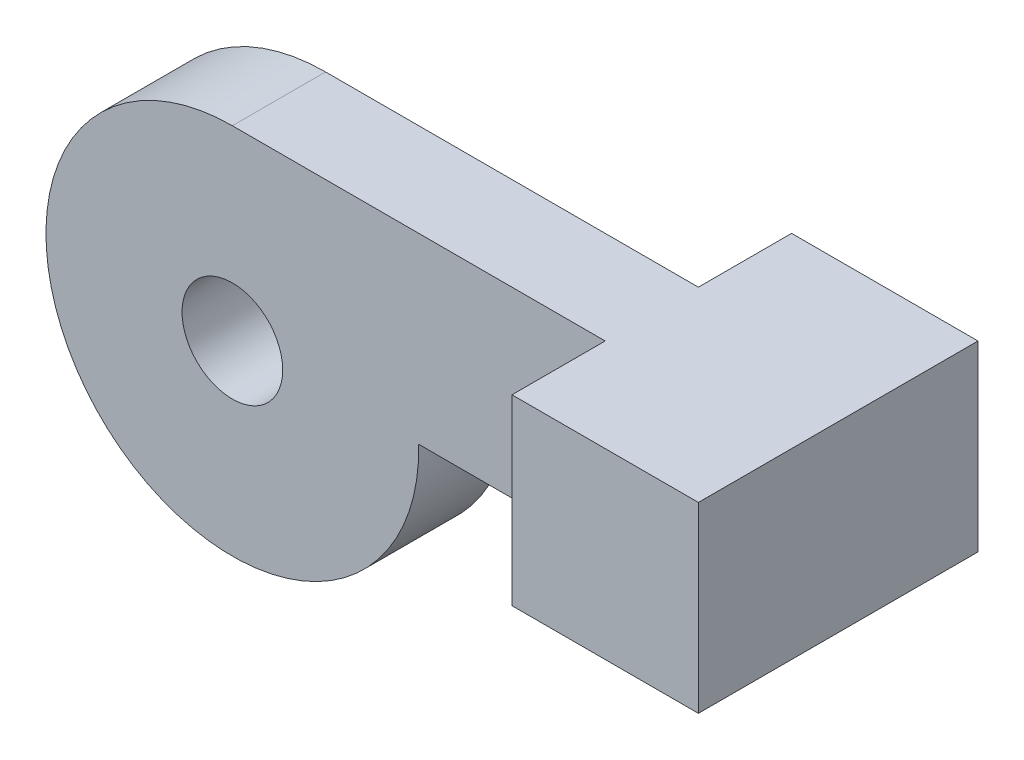
SolidWorks part; units mm, degrees
ref_plane "Front Plane" through (0, 0, 0) normal (0, 0, 1) x (1, 0, 0)
ref_plane "Top Plane" through (0, 0, 0) normal (0, 1, 0) x (1, 0, 0)
ref_plane "Right Plane" through (0, 0, 0) normal (1, 0, 0) x (0, 0, -1)
sketch "Sketch1" plane through (0, 0, 0) normal (0, 0, 1) x (1, 0, 0)
  line L5 (0, 12.7) -> (38.1, 12.7)
  line L6 (38.1, 12.7) -> (38.1, 0.254)
  line L7 (38.1, 0.254) -> (12.6975, 0.254)
  circle A2 centre (0, 0) radius 3.429
  arc A3 (0, 12.7) -> (12.6975, 0.254) centre (0, 0) ccw
  dimension "D3" = 6.858
  dimension "D5" = 25.4
  dimension "D2" = 0.254
  dimension "D4" = 38.1
extrude "Boss-Extrude1" add sketch "Sketch1" along normal mid plane 6.35
sketch "Sketch2" plane through (0, 0, 0) normal (0, 0, 1) x (1, 0, 0)
  line L0 (12.6975, 0.254) -> (38.1, 0.254) construction
  line L1 (38.1, 12.7) -> (25.4, 12.7)
  line L2 (38.1, 12.7) -> (38.1, 0.254)
  line L3 (38.1, 0.254) -> (25.4, 0.254)
  line L4 (25.4, 12.7) -> (25.4, 0.254)
  dimension "D1" = 12.7
extrude "Boss-Extrude2" add sketch "Sketch2" along normal mid plane 19.05
equation "\"tightTol\"= 0.005in"
equation "\"normTol\"= 0.01in"
equation "\"looseTol\"= 0.02in"
equation "\"D2@Sketch1\"=\"normTol\""
equation "\"D3@Sketch1\"=0.25+\"looseTol\""
equation "\"D1\" = \"looseTol\" + 0.250000in"
